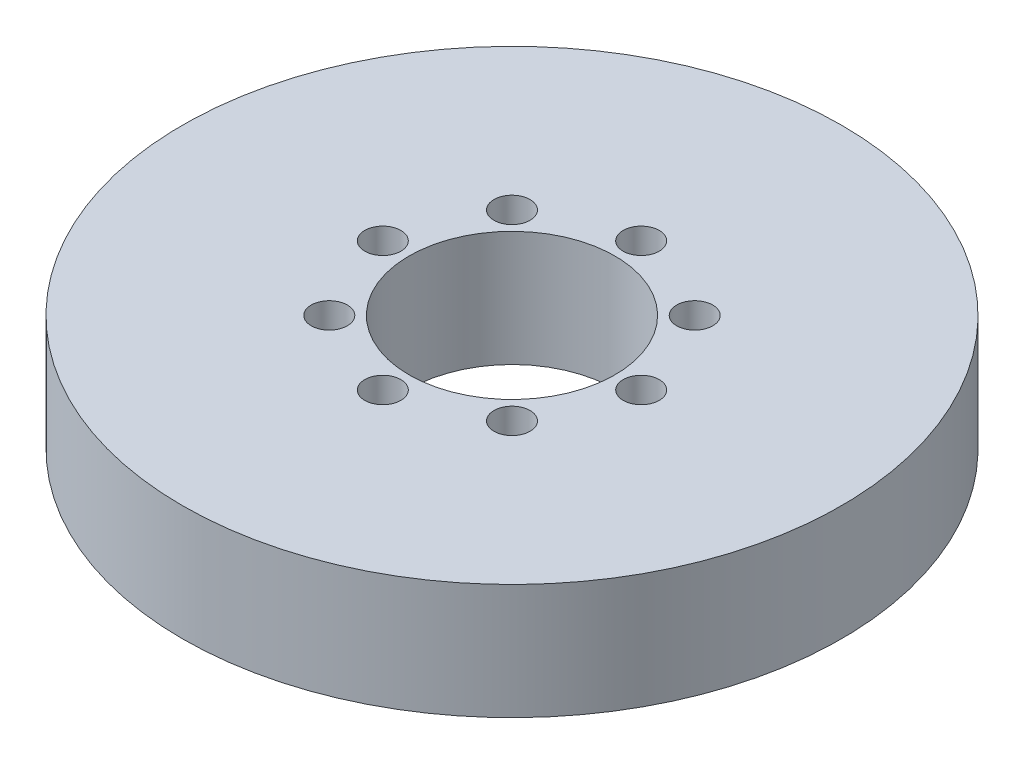
SolidWorks part; units mm, degrees
ref_plane "Front Plane" through (0, 0, 0) normal (0, 0, 1) x (1, 0, 0)
ref_plane "Top Plane" through (0, 0, 0) normal (0, 1, 0) x (1, 0, 0)
ref_plane "Right Plane" through (0, 0, 0) normal (1, 0, 0) x (0, 0, -1)
sketch "Sketch1" plane through (0, 0, 0) normal (0, 1, 0) x (1, 0, 0)
  circle A0 centre (0, 0) radius 40
  dimension "FLANGE_OD" = 80
extrude "Boss-Extrude1" add sketch "Sketch1" along normal blind 14
sketch "Sketch2" plane through (0, 0, 0) normal (0, 1, 0) x (1, 0, 0)
  circle A0 centre (0, 0) radius 12.5
  dimension "BORE_D" = 25
extrude "Cut-Extrude1" cut sketch "Sketch2" along normal through all
sketch "Sketch3" plane through (0, 14, 0) normal (0, 1, 0) x (1, 0, 0)
  circle A0 centre (0, 0) radius 15.6811 construction
  circle A1 centre (-15.6811, 0) radius 2.1904
  dimension "BOLT_D" = 4.3807
  dimension "BOLT_PCD" = 31.3622
extrude "Cut-Extrude2" cut sketch "Sketch3" against normal blind 11.6186
pattern_circular "CirPattern1" count 8 over 360 about axis through (0, 0, 0) along (0, 1, 0) of "Cut-Extrude2"
